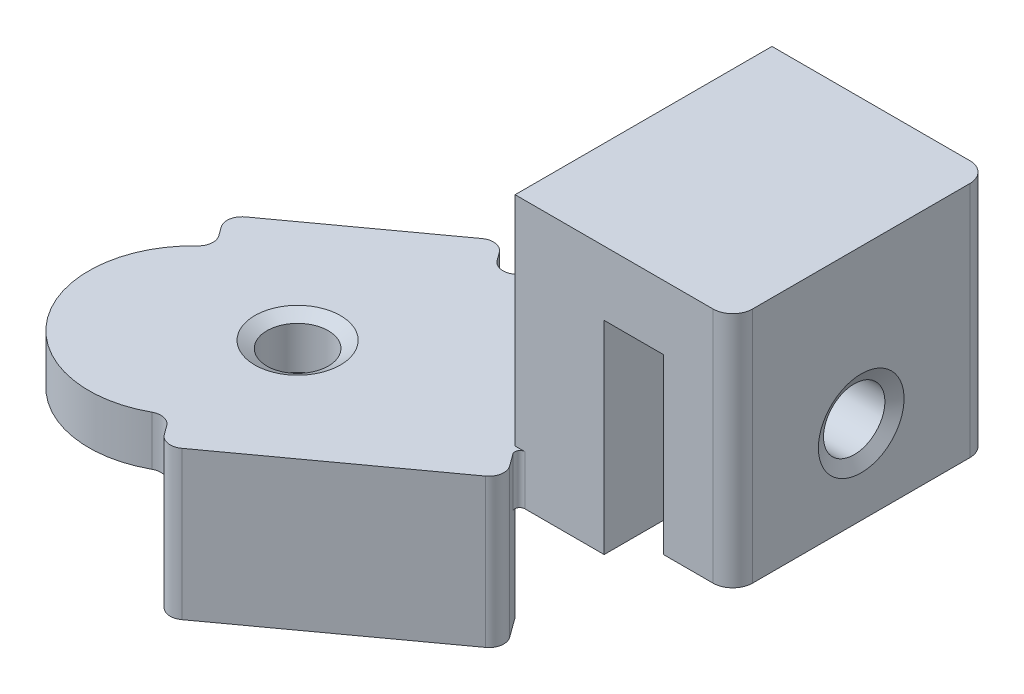
SolidWorks part; units mm, degrees
material "PA 类型 6"
ref_plane "前视基准面" through (0, 0, 0) normal (0, 0, 1) x (1, 0, 0)
ref_plane "上视基准面" through (0, 0, 0) normal (0, 1, 0) x (1, 0, 0)
ref_plane "右视基准面" through (0, 0, 0) normal (1, 0, 0) x (0, 0, -1)
sketch "草图1" plane through (0, 0, 0) normal (0, 1, 0) x (1, 0, 0)
  line L0 (0, 0) -> (0, 12.2017) construction
  line L1 (0, 0) -> (15.21, 0) construction
  line L2 (0, 0) -> (11.3188, 8.2236) construction
  line L3 (10.1244, 13.8452) -> (-6.1542, 2.018)
  line L4 (10.1244, 0.8664) -> (0.0175, -6.4766)
  line L5 (0.0175, -6.4766) -> (-6.1542, 2.018) construction
  line L6 (10.1244, 13.8452) -> (10.1244, 0.8664)
  circle A0 centre (0, 0) radius 1.55
  arc A1 (-6.1542, 2.018) -> (0.0175, -6.4766) centre (-3.0684, -2.2293) ccw
  dimension "D1" = 3.1
  dimension "D2" = 36
  dimension "D3" = 10.5
  dimension "D4" = 10.1244
extrude "基座" add sketch "草图1" along normal blind 2.5
sketch "草图2" plane through (0, 0, 0) normal (0, 1, 0) x (1, 0, 0)
  line L0 (0.0175, -6.4766) -> (1.1931, -8.0947)
  line L1 (1.1931, -8.0947) -> (11.3, -0.7516)
  line L2 (11.3, -0.7516) -> (10.1244, 0.8664)
  line L3 (0.0175, -6.4766) -> (10.1244, 0.8664) construction
  line L4 (10.1244, 0.8664) -> (0.0175, -6.4766)
  line L5 (0, 0) -> (19.4408, 0) construction
  line L6 (0, 0) -> (14.65, 10.6439) construction
  line L7 (10.1244, 13.8452) -> (-6.1542, 2.018) construction
  line L8 (10.1244, 13.8452) -> (-6.1542, 2.018) construction
  line L10 (-7.3298, 3.6361) -> (0.8095, 9.5496)
  line L11 (-6.1542, 2.018) -> (-7.3298, 3.6361)
  line L12 (1.9851, 7.9316) -> (-6.1542, 2.018)
  line L13 (0.8095, 9.5496) -> (1.9851, 7.9316)
  point P20 (1.9851, 7.9316)
  dimension "D1" = 2
extrude "机臂限位" add sketch "草图2" against normal blind 7.5 from surface starting at face at (2.4662, 2.5, -1.7918)
sketch "草图3" plane through (0, 0, 0) normal (0, 1, 0) x (1, 0, 0)
  line L0 (10.1244, 13.8452) -> (14.6244, 13.8452)
  line L1 (14.6244, 13.8452) -> (14.6244, 0.8664)
  line L2 (14.6244, 0.8664) -> (10.1244, 0.8664)
  line L3 (10.1244, 0.8664) -> (10.1244, 13.8452)
  dimension "D1" = 4.5
extrude "限位-1" add sketch "草图3" along normal blind 13.5
sketch "草图4" plane through (0, 0, 0) normal (0, 0, 1) x (1, 0, 0)
  line L0 (14.6244, 13.5) -> (21.1244, 13.5)
  line L1 (21.1244, 13.5) -> (21.1244, 1.5)
  line L2 (21.1244, 1.5) -> (17.6244, 1.5)
  line L3 (17.6244, 1.5) -> (17.6244, 10.25)
  line L4 (17.6244, 10.25) -> (14.6244, 10.25)
  line L5 (14.6244, 13.5) -> (14.6244, 0) construction
  line L6 (14.6244, 10.25) -> (14.6244, 13.5)
  dimension "D1" = 3.25
  dimension "D2" = 3
  dimension "D3" = 8.75
  dimension "D4" = 3.5
extrude "限位-2" add sketch "草图4" against normal up to surface (13.8452 mm away) from surface up to face at (11.9244, 5.9, -13.8452) starting at face at (11.9244, 5.9, -0.8664)
sketch "草图5" plane through (21.1244, 0, 0) normal (1, 0, 0) x (0, 0, -1)
  line L2 (7.3558, 5.75) -> (7.3558, 13.5) construction
  line L3 (13.8452, 13.5) -> (0.8664, 13.5) construction
  line L5 (8.9579, 2.975) -> (10.5601, 5.75)
  line L6 (10.5601, 5.75) -> (8.9579, 8.525)
  line L7 (8.9579, 8.525) -> (5.7537, 8.525)
  line L8 (5.7537, 8.525) -> (4.1515, 5.75)
  line L9 (4.1515, 5.75) -> (5.7537, 2.975)
  line L10 (5.7537, 2.975) -> (8.9579, 2.975)
  circle A0 centre (7.3558, 5.75) radius 1.55
  circle A1 centre (7.3558, 5.75) radius 2.775 construction
  dimension "D1" = 3.1
  dimension "D2" = 5.55
  dimension "D3" = 7.75
extrude "螺丝位" cut sketch "草图5" against normal through all contours A0 region at (21.1244, 5.75, -7.3558)
extrude "螺母位" cut sketch "草图5<3>" along normal blind 2 from surface starting at face at (10.1244, 5.75, -8.9058)
sketch "草图5<3>" plane through (21.1244, 0, 0) normal (1, 0, 0) x (0, 0, -1) same geometry as "草图5"
chamfer "倒角1" distance 0.615 angle 30 2 edges at (21.1244, 7.3, -7.3558) (0, 2.5, 1.55) first distance on face at (21.1244, 7.3, -7.3558) first distance on face at (1.9803, 2.5, -2.1598)
fillet "圆角5" radius 0.75 7 edges at (1.1931, -1.25, 8.0947) (-7.3298, -1.25, -3.6361) (0.0175, 1.25, 6.4766) (-6.1542, 1.25, -2.018) (11.3, -1.25, 0.7516) (1.9851, 1.25, -7.9316) (0.8095, -1.25, -9.5496)
fillet "圆角6" radius 0.25 1 edges at (10.1244, 1.25, -0.8664)
fillet "圆角8" radius 1 2 edges at (21.1244, 7.5, -0.8664) (21.1244, 7.5, -13.8452)
